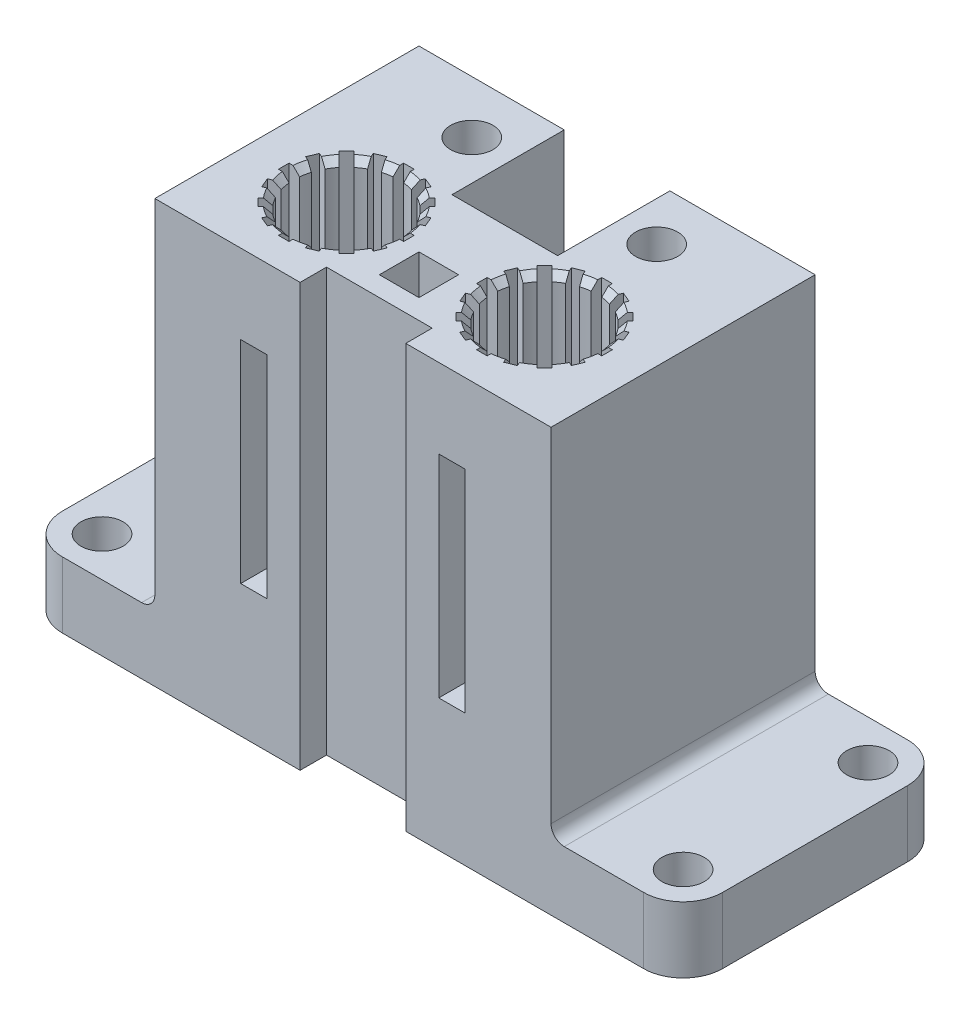
SolidWorks part; units mm, degrees
ref_plane "前视基准面" through (0, 0, 0) normal (0, 0, 1) x (1, 0, 0)
ref_plane "上视基准面" through (0, 0, 0) normal (0, 1, 0) x (1, 0, 0)
ref_plane "右视基准面" through (0, 0, 0) normal (1, 0, 0) x (0, 0, -1)
sketch "草图1" plane through (0, 0, 0) normal (0, 1, 0) x (1, 0, 0)
  line L1 (-15, -10) -> (15, -10)
  line L2 (-15, -10) -> (-15, 10)
  line L3 (-15, 10) -> (15, 10)
  line L4 (15, -10) -> (15, 10)
  line L5 (-15, -10) -> (15, 10) construction
  line L6 (-15, 10) -> (15, -10) construction
  point P0 (0, 0)
  dimension "D1" = 30
  dimension "D2" = 30
  dimension "D3" = 20
extrude "凸台-拉伸1" add sketch "草图1" along normal blind 32
sketch "草图2" plane through (0, 32, 0) normal (0, 1, 0) x (1, 0, 0)
  line L0 (-7.5, -3) -> (7.5, -3) construction
  line L1 (0, 0) -> (0, -3) construction
  line L2 (-15, -10) -> (15, -10) construction
  circle A0 centre (-7.5, -3) radius 3.96
  circle A1 centre (7.5, -3) radius 3.96
  dimension "D1" = 7.92
  dimension "D2" = 15
  dimension "D3" = 7
extrude "切除-拉伸1" cut sketch "草图2" against normal blind 8
sketch "草图3" plane through (0, 24, 0) normal (0, 1, 0) x (1, 0, 0)
  circle A1 centre (-7.5, -3) radius 3.96
  circle A2 centre (-7.5, -3) radius 3.96
  circle A3 centre (7.5, -3) radius 3.96
  circle A4 centre (7.5, -3) radius 3.96
  dimension "D1" = 0
  dimension "D2" = 0
extrude "切除-拉伸2" cut sketch "草图3" against normal blind 12 from offset 12 offset against normal yes
sketch "草图4" plane through (0, 32, 0) normal (0, 1, 0) x (1, 0, 0)
  line L0 (0, 0) -> (0, 10) construction
  line L1 (15, 10) -> (-15, 10) construction
  line L2 (7.5, -3) -> (-7.5, -3) construction
  line L3 (4, 1.5) -> (-4, 1.5)
  line L4 (4, 1.5) -> (4, 10)
  line L5 (4, 10) -> (-4, 10)
  line L6 (-4, 1.5) -> (-4, 10)
  line L7 (4, 1.5) -> (-4, 10) construction
  line L8 (4, 10) -> (-4, 1.5) construction
  circle A0 centre (7.5, -3) radius 3.96 construction
  circle A1 centre (7.5, -3) radius 3.96 construction
  circle A2 centre (-7.5, -3) radius 3.96 construction
  circle A3 centre (-7.5, -3) radius 3.96 construction
  point P5 (0, 5.75)
  dimension "D1" = 8
  dimension "D2" = 4.5
extrude "切除-拉伸3" cut sketch "草图4" against normal blind 25
sketch "草图6" plane through (0, 24, 0) normal (0, 1, 0) x (1, 0, 0)
  circle A0 centre (7.5, -3) radius 3.96 construction
  circle A1 centre (7.5, -3) radius 3.96 construction
  circle A2 centre (-7.5, -3) radius 3.96 construction
  circle A3 centre (-7.5, -3) radius 3.96 construction
  circle A4 centre (7.5, -3) radius 2.25
  circle A5 centre (-7.5, -3) radius 2.25
  dimension "D1" = 4.5
extrude "切除-拉伸5" cut sketch "草图6" against normal through all
sketch "草图5" plane through (0, 0, -10) normal (0, 0, -1) x (-1, 0, 0)
  line L0 (11.46, 24) -> (3.54, 24) construction
  line L1 (11.46, 24) -> (3.54, 24) construction
  line L2 (3.54, 12) -> (11.46, 12) construction
  line L3 (3.54, 12) -> (11.46, 12) construction
  line L4 (7.5, 24) -> (7.5, 12) construction
  line L5 (0, 0) -> (0, 37.272) construction
  line L6 (6.5, 26) -> (8.5, 26)
  line L7 (6.5, 26) -> (6.5, 10)
  line L8 (6.5, 10) -> (8.5, 10)
  line L9 (8.5, 26) -> (8.5, 10)
  line L10 (6.5, 26) -> (8.5, 10) construction
  line L11 (6.5, 10) -> (8.5, 26) construction
  line L12 (-6.5, 26) -> (-8.5, 26)
  line L13 (-6.5, 26) -> (-6.5, 10)
  line L14 (-6.5, 10) -> (-8.5, 10)
  line L15 (-8.5, 26) -> (-8.5, 10)
  point P6 (7.5, 18)
  dimension "D1" = 2
  dimension "D2" = 16
extrude "切除-拉伸4" cut sketch "草图5" against normal through all
sketch "草图7" plane through (0, 32, 0) normal (0, 1, 0) x (1, 0, 0)
  line L0 (0, 0) -> (0, -10) construction
  line L1 (-15, -10) -> (15, -10) construction
  line L3 (4, -8) -> (-4, -8)
  line L4 (4, -8) -> (4, -10)
  line L5 (4, -10) -> (-4, -10)
  line L6 (-4, -8) -> (-4, -10)
  line L7 (4, -8) -> (-4, -10) construction
  line L8 (4, -10) -> (-4, -8) construction
  point P5 (0, -9)
  dimension "D1" = 2
  dimension "D2" = 8
extrude "切除-拉伸6" cut sketch "草图7" against normal through all
sketch "草图8" plane through (0, 0, -10) normal (0, 0, -1) x (-1, 0, 0)
  line L0 (0, 0) -> (0, 32) construction
  line L1 (-15, 32) -> (-4, 32) construction
  line L2 (-15, 32) -> (-15, 0) construction
  line L3 (0, 16) -> (23.025, 16) construction
  line L4 (4, 32) -> (-4, 32) construction
  line L5 (4, 32) -> (-4, 32) construction
  circle A0 centre (-12, 29) radius 1.6
  circle A1 centre (12, 29) radius 1.6
  circle A2 centre (-12, 3) radius 1.6
  circle A3 centre (12, 3) radius 1.6
  point P13 (0, 26.9954)
  point P16 (0, 32)
  dimension "D1" = 3.2
  dimension "D2" = 3
  dimension "D3" = 3
extrude "切除-拉伸7" cut sketch "草图8" against normal blind 6
sketch "草图9" plane through (0, 0, -10) normal (0, 0, -1) x (-1, 0, 0)
  line L0 (0, 0) -> (0, 9.7164) construction
  line L1 (-12.35, 2.65) -> (-9.65, 2.65)
  line L2 (-12.35, 2.65) -> (-12.35, 5.35)
  line L3 (-12.35, 5.35) -> (-9.65, 5.35)
  line L4 (-9.65, 2.65) -> (-9.65, 5.35)
  line L5 (-12.35, 2.65) -> (-9.65, 5.35) construction
  line L6 (-12.35, 5.35) -> (-9.65, 2.65) construction
  line L7 (-15, 0) -> (15, 0) construction
  line L8 (12.35, 2.65) -> (9.65, 2.65)
  line L9 (12.35, 2.65) -> (12.35, 5.35)
  line L10 (12.35, 5.35) -> (9.65, 5.35)
  line L11 (9.65, 2.65) -> (9.65, 5.35)
  line L12 (-15, 32) -> (-15, 0) construction
  point P0 (-11, 4)
  dimension "D1" = 4
  dimension "D2" = 4
  dimension "D3" = 2.7
  dimension "D4" = 2.7
extrude "凸台-拉伸2" [suppressed] add sketch "草图9" along normal blind 4
sketch "草图10" plane through (0, 32, 0) normal (0, 1, 0) x (1, 0, 0)
  line L0 (0, 0) -> (0, 16.0129) construction
  line L1 (13.6, 10) -> (10.4, 10) construction
  line L2 (15, -10) -> (15, 10) construction
  circle A0 centre (7, 6) radius 1.6
  circle A1 centre (-7, 6) radius 1.6
  dimension "D1" = 3.2
  dimension "D2" = 4
  dimension "D3" = 8
extrude "切除-拉伸8" cut sketch "草图10" against normal blind 6
chamfer "倒角1" distance 0.5 angle 45 4 edges at (7.5, 0, 6.96) (-7.5, 0, 6.96) (-7.5, 32, 6.96) (7.5, 32, 6.96)
sketch "草图11" plane through (0, 32, 0) normal (0, 1, 0) x (1, 0, 0)
  line L0 (7.5, -3) -> (2.6179, -3) construction
  line L2 (2.7603, -3.4) -> (3.5603, -3.4)
  line L3 (2.7603, -3.4) -> (2.7603, -2.6)
  line L4 (2.7603, -2.6) -> (3.5603, -2.6)
  line L5 (3.5603, -3.4) -> (3.5603, -2.6)
  line L6 (2.7603, -3.4) -> (3.5603, -2.6) construction
  line L7 (2.7603, -2.6) -> (3.5603, -3.4) construction
  circle A0 centre (7.5, -3) radius 3.96 construction
  circle A1 centre (7.5, -3) radius 3.96 construction
  point P3 (3.1603, -3)
  dimension "D1" = 0.8
  dimension "D2" = 0.8
extrude "切除-拉伸9" cut sketch "草图11" against normal up to surface (8 mm away) up to face at (5.4475, 24, 3)
pattern_circular "阵列(圆周)1" count 16 over 360 about axis through (7.5, 24, 3) along (0, 1, 0) of "切除-拉伸9"
sketch "草图12" plane through (0, 0, 0) normal (0, -1, 0) x (1, 0, 0)
  line L0 (7.5, 3) -> (1.5112, 3) construction
  line L2 (2.7603, 2.6) -> (3.5603, 2.6)
  line L3 (2.7603, 2.6) -> (2.7603, 3.4)
  line L4 (2.7603, 3.4) -> (3.5603, 3.4)
  line L5 (3.5603, 2.6) -> (3.5603, 3.4)
  line L6 (2.7603, 2.6) -> (3.5603, 3.4) construction
  line L7 (2.7603, 3.4) -> (3.5603, 2.6) construction
  circle A0 centre (7.5, 3) radius 3.96 construction
  circle A1 centre (7.5, 3) radius 3.96 construction
  point P4 (3.1603, 3)
  dimension "D1" = 0.8
  dimension "D2" = 0.8
extrude "切除-拉伸10" cut sketch "草图12" against normal up to surface (12 mm away) up to face at (5.4475, 12, 3)
pattern_circular "阵列(圆周)2" count 16 over 360 about axis through (7.5, 12, 3) along (0, 1, 0) of "切除-拉伸10"
mirror "镜向1" about plane through (0, 0, 0) normal (1, 0, 0) of "阵列(圆周)2", "阵列(圆周)1"
sketch "草图13" plane through (0, 32, 0) normal (0, 1, 0) x (1, 0, 0)
  line L0 (0, 0) -> (0, -5) construction
  line L1 (4, -10) -> (15, -10) construction
  line L2 (-1.5, -6.5) -> (1.5, -6.5)
  line L3 (-1.5, -6.5) -> (-1.5, -3.5)
  line L4 (-1.5, -3.5) -> (1.5, -3.5)
  line L5 (1.5, -6.5) -> (1.5, -3.5)
  line L6 (-1.5, -6.5) -> (1.5, -3.5) construction
  line L7 (-1.5, -3.5) -> (1.5, -6.5) construction
  dimension "D1" = 3
  dimension "D2" = 3
  dimension "D3" = 5
extrude "切除-拉伸11" cut sketch "草图13" against normal blind 4
sketch "草图14" plane through (0, 0, 0) normal (0, -1, 0) x (1, 0, 0)
  line L0 (15, -10) -> (-15, -10) construction
  line L1 (15, 10) -> (25, 10)
  line L2 (15, 10) -> (15, -10)
  line L3 (15, -10) -> (25, -10)
  line L4 (25, 10) -> (25, -10)
  line L5 (0, 0) -> (0, -16.1877) construction
  dimension "D1" = 10
extrude "凸台-拉伸3" add sketch "草图14" against normal blind 5
sketch "草图15" plane through (0, 5, 0) normal (0, 1, 0) x (1, 0, 0)
  line L0 (22, 10) -> (22, -10) construction
  line L1 (15, 10) -> (25, 10) construction
  line L2 (25, -10) -> (15, -10) construction
  line L3 (25, 0) -> (32.2189, 0) construction
  line L4 (25, 10) -> (25, -10) construction
  circle A0 centre (22, 7) radius 1.6
  circle A1 centre (22, -7) radius 1.6
  dimension "D1" = 3.2
  dimension "D2" = 14
  dimension "D3" = 3
extrude "切除-拉伸12" cut sketch "草图15" against normal through all
mirror "镜向6" about plane through (0, 0, 0) normal (1, 0, 0) of "切除-拉伸12", "凸台-拉伸3"
fillet "圆角1" radius 1 2 edges at (15, 5, 0) (-15, 5, 0)
fillet "圆角2" radius 3 4 edges at (25, 2.5, -10) (25, 2.5, 10) (-25, 2.5, 10) (-25, 2.5, -10)
